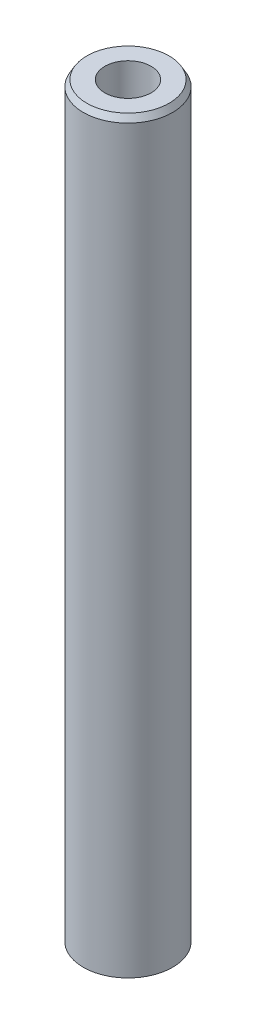
SolidWorks part; units mm, degrees
ref_plane "Front Plane" through (0, 0, 0) normal (0, 0, 1) x (1, 0, 0)
ref_plane "Top Plane" through (0, 0, 0) normal (0, 1, 0) x (1, 0, 0)
ref_plane "Right Plane" through (0, 0, 0) normal (1, 0, 0) x (0, 0, -1)
sketch "Sketch1" plane through (0, 0, 0) normal (0, 1, 0) x (1, 0, 0)
  circle A0 centre (0, 0) radius 10
  dimension "SHAFT_OD" = 20
extrude "Boss-Extrude1" add sketch "Sketch1" along normal blind 167.9204
sketch "Sketch2" plane through (0, 0, 0) normal (0, 1, 0) x (1, 0, 0)
  circle A0 centre (0, 0) radius 5.1713
  dimension "BORE_D" = 10.3425
extrude "Cut-Extrude1" cut sketch "Sketch2" along normal through all
chamfer "Chamfer1" distance 1.3812 angle 30 2 edges at (0, 167.9204, 10) (0, 0, 10) first distance on face at (0, 167.9204, 10) first distance on face at (0, 0, 5.1713)
